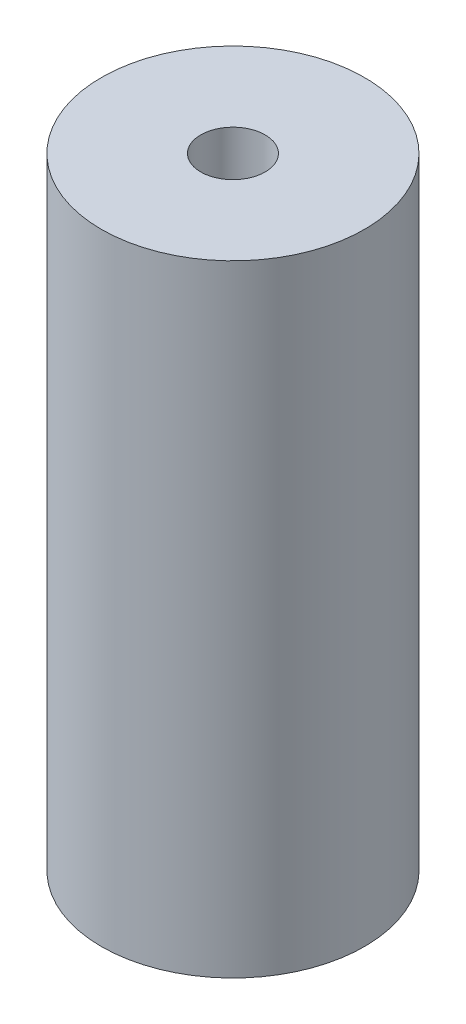
SolidWorks part; units mm, degrees
ref_plane "Front Plane" through (0, 0, 0) normal (0, 0, 1) x (1, 0, 0)
ref_plane "Top Plane" through (0, 0, 0) normal (0, 1, 0) x (1, 0, 0)
ref_plane "Right Plane" through (0, 0, 0) normal (1, 0, 0) x (0, 0, -1)
sketch "Sketch1" plane through (0, 0, 0) normal (0, 1, 0) x (1, 0, 0)
  circle A0 centre (0, 0) radius 11.65
  dimension "D1" = 23.3
extrude "Boss-Extrude1" add sketch "Sketch1" along normal blind 55
sketch "Sketch2" plane through (0, 55, 0) normal (0, 1, 0) x (1, 0, 0)
  circle A0 centre (0, 0) radius 2.85
  dimension "D1" = 5.7
extrude "Cut-Extrude1" cut sketch "Sketch2" against normal blind 110
